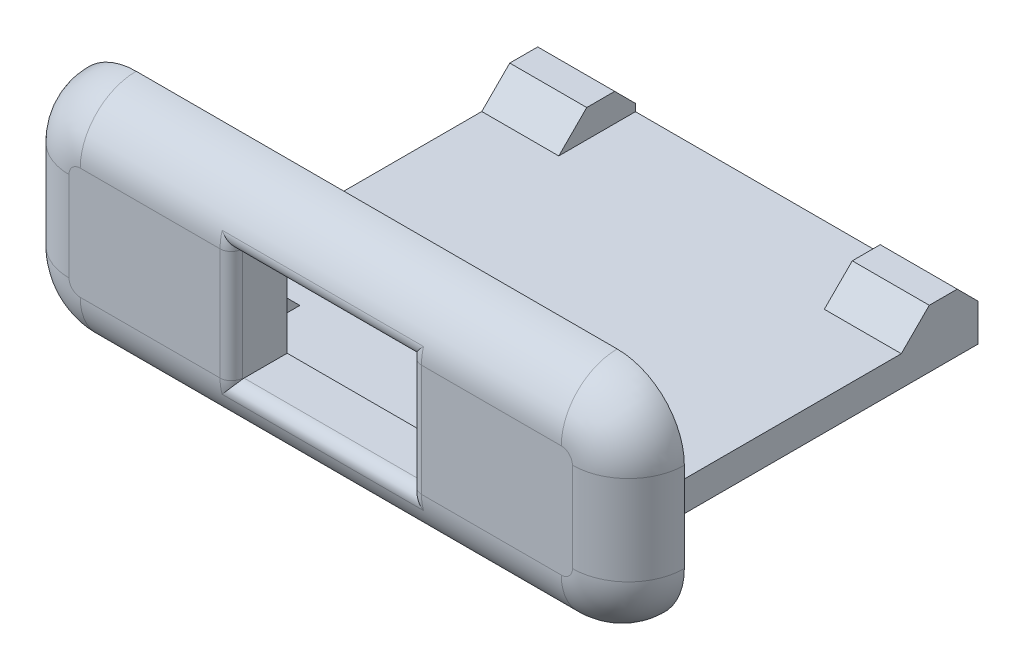
SolidWorks part; units mm, degrees
ref_plane "Спереди" through (0, 0, 0) normal (0, 0, 1) x (1, 0, 0)
ref_plane "Сверху" through (0, 0, 0) normal (0, 1, 0) x (1, 0, 0)
ref_plane "Справа" through (0, 0, 0) normal (1, 0, 0) x (0, 0, -1)
ref_plane "Плоскость4" through (0, 0, 727.8525) normal (0, 0, 1) x (1, 0, 0)
sketch "Эскиз1" plane through (0, 0, 727.8525) normal (0, 0, 1) x (1, 0, 0)
  line L1 (-208.0776, -72.8681) -> (-122.0776, -72.8681)
  line L2 (-220.0776, -84.8681) -> (-220.0776, -100.8681)
  line L3 (-208.0776, -112.8681) -> (-122.0776, -112.8681)
  line L4 (-110.0776, -84.8681) -> (-110.0776, -100.8681)
  arc A0 (-122.0776, -112.8681) -> (-110.0776, -100.8681) centre (-122.0776, -100.8681) ccw
  arc A1 (-122.0776, -72.8681) -> (-110.0776, -84.8681) centre (-122.0776, -84.8681) cw
  arc A2 (-220.0776, -100.8681) -> (-208.0776, -112.8681) centre (-208.0776, -100.8681) ccw
  arc A3 (-208.0776, -72.8681) -> (-220.0776, -84.8681) centre (-208.0776, -84.8681) ccw
  point P6 (-110.0776, -112.8681)
  point P11 (-220.0776, -112.8681)
  point P14 (-220.0776, -72.8681)
  dimension "D3" = 12
  dimension "D1" = 110
  dimension "D2" = 40
extrude "Бобышка-Вытянуть1" add sketch "Эскиз1" along normal blind 10
sketch "Эскиз2" plane through (0, 0, 737.8525) normal (0, 0, 1) x (1, 0, 0)
  line L8 (-220.0776, -92.8681) -> (-110.0776, -92.8681) construction
  line L9 (-220.0776, -84.8681) -> (-220.0776, -100.8681) construction
  line L10 (-110.0776, -100.8681) -> (-110.0776, -84.8681) construction
  line L11 (-165.0776, -72.8681) -> (-165.0776, -112.8681) construction
  line L12 (-122.0776, -72.8681) -> (-208.0776, -72.8681) construction
  line L13 (-208.0776, -112.8681) -> (-122.0776, -112.8681) construction
  line L18 (-181.0776, -82.7081) -> (-181.0776, -103.0281)
  line L19 (-181.0776, -103.0281) -> (-149.0776, -103.0281)
  line L20 (-149.0776, -103.0281) -> (-149.0776, -82.7081)
  line L21 (-149.0776, -82.7081) -> (-181.0776, -82.7081)
  point P2 (-181.0776, -92.8681)
  point P16 (-165.0776, -82.7081)
  dimension "D1" = 20.32
  dimension "D2" = 20.32
  dimension "D3" = 32
extrude "Вырез-Вытянуть1" cut sketch "Эскиз2" against normal up to surface (10 mm away) up to face at (-165.0776, -92.8681, 727.8525)
ref_plane "Плоскость5" through (-165.0776, 0, 0) normal (1, 0, 0) x (0, 0, -1)
ref_plane "Плоскость6" through (0, -103.0281, 0) normal (0, 1, 0) x (1, 0, 0)
ref_plane "Плоскость7" through (0, 0, 727.8525) normal (0, 0, -1) x (-1, 0, 0)
fillet "Скругление1" radius 10 8 edges at (-110.0776, -92.8681, 737.8525) (-113.5923, -109.3534, 737.8525) (-165.0776, -112.8681, 737.8525) (-216.5629, -109.3534, 737.8525) (-220.0776, -92.8681, 737.8525) (-216.5629, -76.3828, 737.8525) (-165.0776, -72.8681, 737.8525) (-113.5923, -76.3828, 737.8525)
fillet "Скругление2" radius 2 8 edges at (-149.0776, -102.9481, 737.8522) (-149.0776, -82.7881, 737.8522) (-181.0776, -82.7881, 737.8522) (-181.0776, -102.9481, 737.8522) (-149.0776, -92.8681, 737.8525) (-165.0776, -82.7081, 737.8512) (-181.0776, -92.8681, 737.8525) (-165.0776, -103.0281, 737.8512)
sketch "Эскиз3" plane through (0, 0, 727.8525) normal (0, 0, -1) x (-1, 0, 0)
  line L0 (139.2007, -104.4966) -> (92.1307, -104.4966) construction
  line L1 (127.5776, -104.4966) -> (202.5776, -104.4966)
  line L2 (127.5776, -104.4966) -> (127.5776, -112.8681)
  line L3 (127.5776, -112.8681) -> (202.5776, -112.8681)
  line L4 (202.5776, -104.4966) -> (202.5776, -112.8681)
  line L5 (165.0776, -72.8681) -> (165.0776, -133.1733) construction
  line L6 (122.0776, -72.8681) -> (208.0776, -72.8681) construction
  point P6 (165.0776, -104.4966)
  dimension "D1" = 75
  dimension "D4" = 8.3715
extrude "Бобышка-Вытянуть2" add sketch "Эскиз3" along normal blind 70
sketch "Эскиз4" plane through (0, -104.4966, 0) normal (0, 1, 0) x (1, 0, 0)
  line L0 (-202.5776, -657.8525) -> (-202.5776, -727.8525) construction
  line L1 (-202.5776, -661.5629) -> (-188.8126, -661.5629)
  line L2 (-202.5776, -661.5629) -> (-202.5776, -666.5629)
  line L3 (-202.5776, -666.5629) -> (-188.8126, -666.5629)
  line L4 (-188.8126, -661.5629) -> (-188.8126, -666.5629)
  line L5 (-141.3426, -661.5629) -> (-127.5776, -661.5629)
  line L6 (-141.3426, -661.5629) -> (-141.3426, -666.5629)
  line L7 (-141.3426, -666.5629) -> (-127.5776, -666.5629)
  line L8 (-127.5776, -661.5629) -> (-127.5776, -666.5629)
  line L9 (-202.5776, -722.8525) -> (-188.8126, -722.8525)
  line L10 (-202.5776, -722.8525) -> (-202.5776, -727.8525)
  line L11 (-202.5776, -727.8525) -> (-188.8126, -727.8525)
  line L12 (-188.8126, -722.8525) -> (-188.8126, -727.8525)
  line L13 (-122.0776, -727.8525) -> (-208.0776, -727.8525) construction
  line L14 (-127.5776, -657.8525) -> (-127.5776, -727.8525) construction
  line L15 (-141.3426, -727.8525) -> (-127.5776, -727.8525)
  line L16 (-141.3426, -727.8525) -> (-141.3426, -722.8525)
  line L17 (-141.3426, -722.8525) -> (-127.5776, -722.8525)
  line L18 (-127.5776, -727.8525) -> (-127.5776, -722.8525)
  dimension "D1" = 5
  dimension "D2" = 5
  dimension "D3" = 5
  dimension "D4" = 5
  dimension "D5" = 13.765
  dimension "D6" = 13.765
  dimension "D7" = 13.765
  dimension "D8" = 13.765
extrude "Бобышка-Вытянуть3" add sketch "Эскиз4" along normal blind 5
chamfer "Фаска1" distance 5 angle 45 8 edges at (-195.6951, -99.4966, 727.8525) (-134.4601, -99.4966, 727.8525) (-134.4601, -104.4966, 666.5629) (-134.4601, -104.4966, 722.8525) (-134.4601, -104.4966, 661.5629) (-195.6951, -104.4966, 661.5629) (-195.6951, -104.4966, 722.8525) (-195.6951, -104.4966, 666.5629)
sketch "Эскиз5" plane through (0, -112.8681, 0) normal (0, -1, 0) x (1, 0, 0)
  line L4 (-127.5776, 727.8525) -> (-202.5776, 727.8525)
  line L5 (-202.5776, 727.8525) -> (-202.5776, 657.8525)
  line L6 (-202.5776, 657.8525) -> (-127.5776, 657.8525)
  line L7 (-127.5776, 657.8525) -> (-127.5776, 727.8525)
  line L8 (-127.5776, 727.8525) -> (-202.5776, 727.8525)
  line L9 (-202.5776, 727.8525) -> (-202.5776, 657.8525)
  line L10 (-202.5776, 657.8525) -> (-127.5776, 657.8525)
  line L11 (-127.5776, 657.8525) -> (-127.5776, 727.8525)
  dimension "D1" = 0
extrude "Вырез-Вытянуть2" cut sketch "Эскиз5" against normal blind 3
